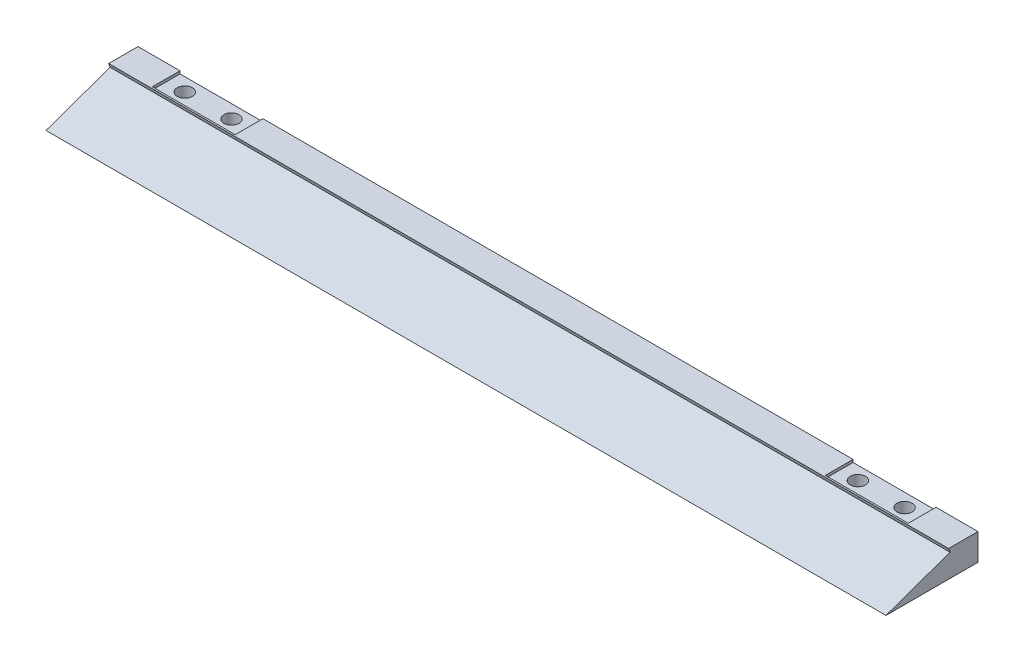
SolidWorks part; units mm, degrees
material "1023 Carbon Steel Sheet (SS)"
ref_plane "Front Plane" through (0, 0, 0) normal (0, 0, 1) x (1, 0, 0)
ref_plane "Top Plane" through (0, 0, 0) normal (0, 1, 0) x (1, 0, 0)
ref_plane "Right Plane" through (0, 0, 0) normal (1, 0, 0) x (0, 0, -1)
sketch "Sketch1" plane through (0, 0, 0) normal (0, 1, 0) x (1, 0, 0)
  line L1 (-100, -15) -> (100, -15)
  line L2 (-100, -15) -> (-100, 15)
  line L3 (-100, 15) -> (100, 15)
  line L4 (100, -15) -> (100, 15)
  line L5 (-100, -15) -> (100, 15) construction
  line L6 (-100, 15) -> (100, -15) construction
  point P0 (0, 0)
  dimension "D1" = 200
  dimension "D2" = 30
extrude "Base" add sketch "Sketch1" along normal blind 6.35
ref_plane "Midplane" through (0, 0, 0) normal (1, 0, 0) x (0, 0, -1)
sketch "Sketch2" plane through (100, 0, 0) normal (1, 0, 0) x (0, 0, -1)
  line L0 (-6.9075, 0) -> (11, 6.35)
  line L1 (-15, 0) -> (15, 0) construction
  line L2 (-15, 6.35) -> (15, 6.35) construction
  line L3 (11, 6.35) -> (11, 0)
  line L4 (11, 0) -> (-6.9075, 0)
  line L5 (15, 6.35) -> (15, 0) construction
  line L7 (11, 6.35) -> (-15, 6.35)
  line L8 (-15, 6.35) -> (-15, 0)
  line L9 (-15, 0) -> (-6.9075, 0)
  line L10 (8.3421, 5.4075) -> (8.0079, 6.35)
  line M3 (-15, 0) -> (15, 0)
  line M5 (15, 6.35) -> (-15, 6.35)
  line M6 (-15, 6.35) -> (-15, 0)
  dimension "D1" = 19
  dimension "D2" = 4
  dimension "D3" = 1
extrude "WedgeCut" cut sketch "Sketch2" against normal up to next contours L0 M3 M5 M6 region at (100, 3.7005, 5.8885)
sketch "Sketch3" plane through (0, 6.35, 0) normal (0, 1, 0) x (1, 0, 0)
  line L0 (-100, 15) -> (-100, 8.0079) construction
  line L1 (-90, 8.396) -> (-70.254, 8.396)
  line L2 (-90, 8.396) -> (-90, 15)
  line L3 (-90, 15) -> (-70.254, 15)
  line L4 (-70.254, 8.396) -> (-70.254, 15)
  line L5 (-90, 8.396) -> (-70.254, 15) construction
  line L6 (-90, 15) -> (-70.254, 8.396) construction
  line L7 (70.254, 15) -> (90, 15)
  line L8 (70.254, 15) -> (70.254, 8.396)
  line L9 (70.254, 8.396) -> (90, 8.396)
  line L10 (90, 15) -> (90, 8.396)
  line L11 (70.254, 15) -> (90, 8.396) construction
  line L12 (70.254, 8.396) -> (90, 15) construction
  line L13 (100, 15) -> (-100, 15) construction
  line L14 (100, 8.0079) -> (100, 15) construction
  point P0 (-80.127, 11.698)
  point P5 (80.127, 11.698)
  dimension "D1" = 6.604
  dimension "D2" = 19.746
  dimension "D3" = 10
  dimension "D4" = 19.746
  dimension "D5" = 10
  dimension "D6" = 6.604
extrude "Hinge Cutout" cut sketch "Sketch3" against normal blind 0.635
sketch "Sketch4" plane through (0, 5.715, 0) normal (0, 1, 0) x (1, 0, 0)
  line L0 (90, 15) -> (70.254, 15) construction
  circle A0 centre (74.5644, 11.825) radius 1.8034
  circle A1 centre (85.6896, 11.825) radius 1.8034
  point P6 (80.127, 15)
  dimension "D5" = 3.6068
  dimension "D6" = 3.6068
  dimension "D1" = 5.5626
  dimension "D2" = 5.5626
  dimension "D3" = 3.175
  dimension "D4" = 3.175
extrude "Hinge Hole Cut" cut sketch "Sketch4" against normal up to next
sketch "Sketch5" plane through (0, 0, 0) normal (0, -1, 0) x (1, 0, 0)
  line L1 (72.0394, -14.35) -> (77.0894, -14.35)
  line L2 (72.0394, -14.35) -> (72.0394, -9.3)
  line L3 (72.0394, -9.3) -> (77.0894, -9.3)
  line L4 (77.0894, -14.35) -> (77.0894, -9.3)
  line L5 (72.0394, -14.35) -> (77.0894, -9.3) construction
  line L6 (72.0394, -9.3) -> (77.0894, -14.35) construction
  line L7 (83.1646, -14.35) -> (88.2146, -14.35)
  line L8 (83.1646, -14.35) -> (83.1646, -9.3)
  line L9 (83.1646, -9.3) -> (88.2146, -9.3)
  line L10 (88.2146, -14.35) -> (88.2146, -9.3)
  line L11 (83.1646, -14.35) -> (88.2146, -9.3) construction
  line L12 (83.1646, -9.3) -> (88.2146, -14.35) construction
  point P0 (74.5644, -11.825)
  point P6 (85.6896, -11.825)
  dimension "D1" = 5.05
  dimension "D2" = 5.05
  dimension "D3" = 5.05
  dimension "D4" = 5.05
extrude "Hinge Nut Cut" cut sketch "Sketch5" against normal blind 2
mirror "Hinge Hole Mirror" about plane through (0, 0, 0) normal (1, 0, 0) of "Hinge Nut Cut", "Hinge Hole Cut"
sketch "Sketch6" plane through (0, 0, 0) normal (0, -1, 0) x (-1, 0, 0)
  circle A0 centre (-80, 5) radius 4.7625
  circle A1 centre (-40, 5) radius 4.7625
  circle A2 centre (0, 5) radius 4.7625
  circle A3 centre (40, 5) radius 4.7625
  circle A4 centre (80, 5) radius 4.7625
  point P10 (0, 0)
  point P11 (0, 0)
  point P12 (0, 0)
  point P13 (0, 5.3734)
  dimension "D1" = 40
  dimension "D2" = 40
  dimension "D3" = 40
  dimension "D4" = 40
  dimension "D5" = 9.525
  dimension "D6" = 5
extrude "Cut-Extrude1" cut sketch "Sketch6" against normal blind 1.5875
